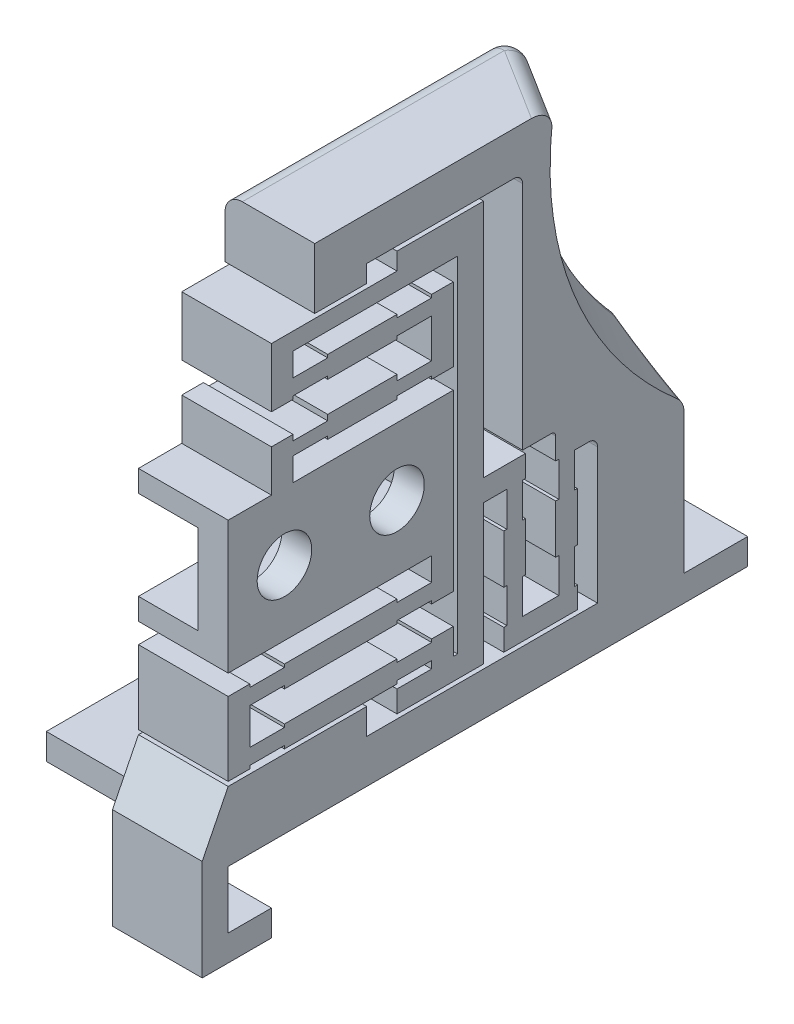
SolidWorks part; units mm, degrees
other "Markup1"
sketch "Sketch8" plane through (10.5, 0, 3) normal (0.7095, 0.0467, 0.7031) x (0.7044, -0.0184, -0.7096)
ref_plane "Front Plane" through (0, 0, 0) normal (0, 0, 1) x (1, 0, 0)
ref_plane "Top Plane" through (0, 0, 0) normal (0, 1, 0) x (1, 0, 0)
ref_plane "Right Plane" through (0, 0, 0) normal (1, 0, 0) x (0, 0, -1)
sketch "Sketch1" plane through (0, 0, 0) normal (1, 0, 0) x (0, 0, -1)
  line L0 (-1.25, -11.3333) -> (8, -11.3333)
  line L1 (8, -11.3333) -> (8, -21.4)
  line L2 (-5, -11.3333) -> (-5, -18.9833)
  line L3 (-5, -18.9833) -> (6.75, -18.9833)
  line L56 (6.75, -20.325) -> (4.75, -20.325)
  line L57 (-3.75, -21.225) -> (-3.75, -23.325)
  line L58 (-3.75, -23.325) -> (-1.75, -23.325)
  line L59 (8, -23.15) -> (8, -24.65)
  line L60 (6.75, -18.9833) -> (6.75, -20.325)
  line L61 (4.75, -20.325) -> (4.75, -20.15)
  line L62 (-5, -20.15) -> (-5, -24.4)
  line L63 (-1.75, -23.325) -> (-1.75, -23.15)
  line L64 (8.25, -4.75) -> (8.25, -24.65)
  line L65 (-1.25, -9.9917) -> (0.75, -9.9917)
  line L66 (6.75, -9.2417) -> (6.75, -6.9917)
  line L67 (6.75, -6.9917) -> (4.75, -6.9917)
  line L68 (-2.5, -7.1667) -> (-2.5, -3.75)
  line L69 (-1.25, -11.3333) -> (-1.25, -9.9917)
  line L70 (0.75, -9.9917) -> (0.75, -10.1667)
  line L71 (8, -10.1667) -> (8, -5.9167)
  line L72 (4.75, -6.9917) -> (4.75, -7.1667)
  line L73 (-1.25, -6.0917) -> (-1.25, -4.75)
  line L74 (-1.25, -4.75) -> (8.25, -4.75)
  line L75 (-2.5, -3.75) -> (4.75, -3.75)
  line L76 (0.75, -10.1667) -> (4.75, -10.1667)
  line L77 (4.75, -10.1667) -> (4.75, -9.9917)
  line L78 (4.75, -9.9917) -> (6.75, -9.9917)
  line L79 (6.75, -9.9917) -> (6.75, -10.1667)
  line L80 (6.75, -10.1667) -> (8, -10.1667)
  line L81 (6.75, -9.2417) -> (4.75, -9.2417)
  line L82 (4.75, -9.2417) -> (4.75, -8.9167)
  line L83 (4.75, -8.9167) -> (0.75, -8.9167)
  line L84 (0.75, -8.9167) -> (0.75, -9.2417)
  line L85 (0.75, -9.2417) -> (-1.25, -9.2417)
  line L86 (-1.25, -9.2417) -> (-1.25, -8.9167)
  line L87 (-1.25, -8.9167) -> (-2.5, -8.9167)
  line L88 (4.75, -7.1667) -> (0.75, -7.1667)
  line L89 (0.75, -7.1667) -> (0.75, -6.9917)
  line L90 (0.75, -6.9917) -> (-1.25, -6.9917)
  line L91 (-1.25, -6.9917) -> (-1.25, -7.1667)
  line L92 (-1.25, -7.1667) -> (-2.5, -7.1667)
  line L93 (-1.25, -6.0917) -> (0.75, -6.0917)
  line L94 (0.75, -6.0917) -> (0.75, -5.9167)
  line L95 (0.75, -5.9167) -> (4.75, -5.9167)
  line L96 (4.75, -5.9167) -> (4.75, -6.0917)
  line L97 (4.75, -6.0917) -> (6.75, -6.0917)
  line L98 (6.75, -6.0917) -> (6.75, -5.9167)
  line L99 (6.75, -5.9167) -> (8, -5.9167)
  line L100 (4.75, -20.15) -> (-1.75, -20.15)
  line L101 (-1.75, -20.15) -> (-1.75, -20.325)
  line L102 (-1.75, -20.325) -> (-3.75, -20.325)
  line L103 (-3.75, -20.325) -> (-3.75, -20.15)
  line L104 (-3.75, -20.15) -> (-5, -20.15)
  line L105 (8, -21.4) -> (6.75, -21.4)
  line L106 (6.75, -21.4) -> (6.75, -21.225)
  line L107 (6.75, -21.225) -> (4.75, -21.225)
  line L108 (4.75, -21.225) -> (4.75, -21.4)
  line L109 (4.75, -21.4) -> (-1.75, -21.4)
  line L110 (-1.75, -21.4) -> (-1.75, -21.225)
  line L111 (-1.75, -21.225) -> (-3.75, -21.225)
  line L112 (-1.75, -23.15) -> (4.75, -23.15)
  line L113 (4.75, -23.15) -> (4.75, -23.325)
  line L114 (4.75, -23.325) -> (6.75, -23.325)
  line L115 (6.75, -23.325) -> (6.75, -23.15)
  line L116 (6.75, -23.15) -> (8, -23.15)
  line L117 (-5, -24.4) -> (-3.75, -24.4)
  line L118 (-3.75, -24.4) -> (-3.75, -24.225)
  line L119 (-3.75, -24.225) -> (-1.75, -24.225)
  line L120 (-1.75, -24.225) -> (-1.75, -24.4)
  line L121 (-1.75, -24.4) -> (4.75, -24.4)
  line L122 (4.75, -24.4) -> (4.75, -24.225)
  line L123 (4.75, -24.225) -> (6.75, -24.225)
  line L124 (6.75, -24.225) -> (6.75, -24.65)
  line L125 (8.25, -24.65) -> (8, -24.65)
  line L126 (6.75, -24.65) -> (4.75, -24.65)
  line L127 (4.75, -24.65) -> (4.75, -25.9)
  line L128 (4.75, -25.9) -> (9.75, -25.9)
  line L130 (14.0917, -24.65) -> (11.9917, -24.65)
  line L131 (11.9917, -24.65) -> (11.9917, -22.65)
  line L132 (11.9917, -22.65) -> (12.1667, -22.65)
  line L133 (12.1667, -22.65) -> (12.1667, -19.8333)
  line L134 (12.1667, -19.8333) -> (11.9917, -19.8333)
  line L135 (11.9917, -19.8333) -> (11.9917, -17.8333)
  line L136 (11.9917, -17.8333) -> (12.1667, -17.8333)
  line L137 (14.0917, -17.8333) -> (14.0917, -19.8333)
  line L138 (14.0917, -19.8333) -> (13.9167, -19.8333)
  line L139 (13.9167, -19.8333) -> (13.9167, -22.65)
  line L140 (13.9167, -22.65) -> (14.0917, -22.65)
  line L141 (14.0917, -22.65) -> (14.0917, -24.65)
  line L145 (11.0917, -24.65) -> (10.9167, -24.65)
  line L146 (11.0917, -24.65) -> (11.0917, -22.65)
  line L147 (11.0917, -22.65) -> (10.9167, -22.65)
  line L148 (10.9167, -22.65) -> (10.9167, -19.8333)
  line L149 (10.9167, -19.8333) -> (11.0917, -19.8333)
  line L150 (11.0917, -17.8333) -> (9.75, -17.8333)
  line L151 (11.0917, -19.8333) -> (11.0917, -17.8333)
  line L153 (9.75, -16.5833) -> (12.1667, -16.5833)
  line L155 (15.8333, -17.8333) -> (14.9917, -17.8333)
  line L156 (14.9917, -17.8333) -> (14.9917, -19.8333)
  line L157 (14.9917, -19.8333) -> (15.1667, -19.8333)
  line L158 (15.1667, -19.8333) -> (15.1667, -22.65)
  line L159 (15.1667, -22.65) -> (14.9917, -22.65)
  line L160 (14.9917, -22.65) -> (14.9917, -24.65)
  line L168 (16.3333, -26.15) -> (16.3333, -18.3333)
  line L179 (16.3333, -26.15) -> (3, -26.15)
  line L180 (3, -26.15) -> (3, -24.65)
  line L181 (3, -24.65) -> (-5, -24.65)
  line L184 (-5, -28.65) -> (21.3333, -28.65)
  line L187 (21.3333, 0) -> (0, 0)
  line L189 (9.75, -25.9) -> (9.75, -17.8333)
  line L190 (3, -3.5) -> (0, -3.5)
  line L191 (0, -3.5) -> (0, 0)
  line L192 (15.1667, -24.65) -> (14.9917, -24.65)
  line L193 (13.6667, -16.3333) -> (12, -16.3333)
  line L194 (12, -16.3333) -> (12, -3)
  line L198 (10.9167, -24.65) -> (10.9167, -25.9)
  line L199 (15.1667, -24.65) -> (15.1667, -25.9)
  line L200 (15.1667, -25.9) -> (10.9167, -25.9)
  line L201 (9.75, -16.5833) -> (9.75, -2.75)
  line L203 (13.9167, -17.8333) -> (13.9167, -16.5833)
  line L204 (12.1667, -17.8333) -> (12.1667, -16.5833)
  line L205 (13.9167, -17.8333) -> (14.0917, -17.8333)
  line L208 (-5, -28.65) -> (-5, -31.98)
  line L209 (-5, -31.98) -> (-2.5, -31.98)
  line L210 (-2.5, -31.98) -> (-2.5, -33.48)
  line L211 (-2.5, -33.48) -> (-6.5, -33.48)
  line L212 (-6.5, -33.48) -> (-6.5, -27.65)
  line L213 (-6.5, -27.65) -> (-5, -24.65)
  line L214 (-2.5, -11.3333) -> (-5, -11.3333)
  line L215 (-2.5, -11.3333) -> (-2.5, -8.9167)
  line L216 (21.3333, 0) -> (21.3333, -28.65)
  line L217 (3, -3.5) -> (3, -2.5)
  line L218 (3, -2.5) -> (11.5, -2.5)
  line L219 (4.75, -3.75) -> (4.75, -2.75)
  line L220 (4.75, -2.75) -> (9.75, -2.75)
  arc A4 (15.8333, -17.8333) -> (16.3333, -18.3333) centre (15.8333, -18.3333) cw
  arc A5 (13.9167, -16.5833) -> (13.6667, -16.3333) centre (13.6667, -16.5833) ccw
  arc A6 (11.5, -2.5) -> (12, -3) centre (11.5, -3) cw
  point P120 (12, -3.5)
  point P140 (16.3333, -17.8333)
  point P144 (13.9167, -16.3333)
  point P159 (-1.875, -7.1667)
  point P199 (14.9917, -23.65)
  dimension "D61" = 0.5
  dimension "D62" = 0.25
  dimension "D66" = 0.5
  dimension "D3" = 4.25
  dimension "D4" = 0.175
  dimension "D5" = 1.25
  dimension "D6" = 0.9
  dimension "D7" = 1.75
  dimension "D8" = 0.175
  dimension "D9" = 0.9
  dimension "D10" = 1.1667
  dimension "D11" = 0.25
  dimension "D13" = 4.25
  dimension "D14" = 1.1667
  dimension "D15" = 0.175
  dimension "D16" = 1.25
  dimension "D17" = 0.75
  dimension "D18" = 1.75
  dimension "D19" = 0.175
  dimension "D21" = 0.9
  dimension "D22" = 1.1667
  dimension "D23" = 1
  dimension "D24" = 0.25
  dimension "D25" = 0.25
  dimension "D34" = 2.5
  dimension "D35" = 2
  dimension "D36" = 2
  dimension "D37" = 1.25
  dimension "D38" = 1.25
  dimension "D40" = 0.25
  dimension "D41" = 1.25
  dimension "D42" = 1.1667
  dimension "D43" = 0.175
  dimension "D44" = 0.9
  dimension "D45" = 1.75
  dimension "D46" = 0.175
  dimension "D47" = 0.9
  dimension "D48" = 1.25
  dimension "D12" = 7.65
  dimension "D20" = 1.5
  dimension "D26" = 1.25
  dimension "D27" = 1.1667
  dimension "D28" = 0.25
  dimension "D32" = 2
  dimension "D33" = 1.25
  dimension "D49" = 2.25
  dimension "D50" = 0.25
  dimension "D39" = 13
  dimension "D30" = 2
  dimension "D53" = 1.5
  dimension "D57" = 1.5
  dimension "D58" = 3.33
  dimension "D59" = 4
  dimension "D31" = 3.5
  dimension "D54" = 5
  dimension "D55" = 1.25
  dimension "D60" = 1
  dimension "D63" = 2
  dimension "D65" = 2.5
  dimension "D64" = 2.5
  dimension "D51" = 5
  dimension "D29" = 1.75
  dimension "D52" = 0.25
  dimension "D56" = 1
extrude "Boss-Extrude1" add sketch "Sketch1" along normal blind 5.18
sketch "Sketch2" plane through (0, 0, 5) normal (0, 0, 1) x (1, 0, 0)
  line L0 (5.18, -11.3333) -> (5.18, -18.9833) construction
  line L1 (5.18, -17.7333) -> (1.73, -17.7333)
  line L2 (5.18, -17.7333) -> (5.18, -12.5833)
  line L3 (5.18, -12.5833) -> (1.73, -12.5833)
  line L4 (1.73, -17.7333) -> (1.73, -12.5833)
  line L5 (5.18, -11.3333) -> (5.18, -18.9833) construction
  dimension "D1" = 3.45
  dimension "D2" = 1.25
  dimension "D3" = 1.25
extrude "Cut-Extrude4" cut sketch "Sketch2" against normal up to next
sketch "Sketch3" plane through (0, -28.65, 0) normal (0, -1, 0) x (1, 0, 0)
  line L1 (0, -25) -> (10.5, -25)
  line L2 (0, -25) -> (0, 5)
  line L3 (0, 5) -> (10.5, 5)
  line L4 (10.5, -25) -> (10.5, 5)
  line L5 (5.18, 5) -> (5.18, -21.3333) construction
  line L8 (0, 5) -> (0, -21.3333) construction
  circle A0 centre (7.92, -10.23) radius 1.575
  circle A1 centre (7.92, -22.23) radius 1.575
  dimension "D3" = 3.15
  dimension "D1" = 10.5
  dimension "D2" = 2.74
  dimension "D4" = 12
  dimension "D5" = 30
  dimension "D6" = 15.23
sketch "Sketch7" plane through (0, 0, 0) normal (-1, 0, 0) x (0, 0, 1)
  line L0 (2.5, -11.3333) -> (5, -11.3333) construction
  line L1 (5, -11.3333) -> (5, -18.9833) construction
  circle A0 centre (1.75, -15.2083) radius 1.575
  circle A1 centre (-4.75, -15.2083) radius 1.575
  dimension "D1" = 3.15
  dimension "D2" = 3.875
  dimension "D3" = 3.25
  dimension "D4" = 6.5
extrude "Cut-Extrude3" cut sketch "Sketch7" against normal up to next
extrude "Boss-Extrude2" add sketch "Sketch3" against normal blind 1.5
mirror "Mirror1" [suppressed] of bodies 111
delete or keep bodies "Body-Delete/Keep 1" [suppressed] type delete bodies bodies 111
ref_plane "Plane1" through (5.2923, 0, -3.3147) normal (-0.8475, 0, 0.5308) x (0, -1, 0)
sketch "Sketch10" plane through (5.2923, 0, -3.3147) normal (-0.8475, 0, 0.5308) x (0, -1, 0)
  line L1 (28.65, 4.2375) -> (28.65, -21.1873) construction
  line L2 (28.65, 9.8109) -> (28.65, -36.5965) construction
  circle A0 centre (3, -33.2691) radius 21.75
  dimension "D2" = 43.5
  dimension "D1" = 43.08
  dimension "D3" = 25.65
extrude "Cut-Extrude5" cut sketch "Sketch10" against normal blind 25
fillet "Fillet1" radius 1 5 edges at (2.7415, -17.0009, -21.3333) (2.59, 0, -15.4594) (5.18, -21.2244, -21.3333) (5.18, -7.9863, -17.5198) (5.18, 0, -8.5408)
mirror "Mirror2" about plane through (0, -18.3333, -15.8333) normal (-1, 0, 0) of bodies 113
delete or keep bodies "Body-Delete/Keep 2" type delete bodies bodies 113
equation "\"VerticalFlexureWidth\"= 1.3"
equation "\"VerticalFlexureGap\"= 1"
equation "\"VerticalDoubleFlexureWidth\"= 2 * \"VerticalFlexureWidth\" + \"VerticalFlexureGap\""
equation "\"HorizontalFlexureLength\"= 7"
equation "\"FlexureJointWidth\"= 1.25"
equation "\"HeadHeight\"= 7.5"
equation "\"VerticalFlexureLength\"= 18"
equation "\"MinGap\"= 0.25"
equation "\"BaseplateHeight+Tolerance\"= 3.33"
equation "\"HeadWidth\"= 13"
equation "\"D1@Boss-Extrude1\"=5.18"
equation "\"HorizontalFlexureWidth\"= 1"
equation "\"HorizontalFlexureGap\"= 1"
equation "\"HorizontalDoubleFlexureWidth\"= 2 * \"HorizontalFlexureWidth\" + \"HorizontalFlexureGap\""
equation "\"FlexureWidth\"= 0.9"
equation "\"FlexureWideWidth\"=1.25"
equation "\"FlexureGap\"=1.75"
equation "\"TwinFlexureWidth\"= \"FlexureGap\" + 2 * \"FlexureWideWidth\""
equation "\"D3@Sketch1\"=\"TwinFlexureWidth\""
equation "\"FlexureNeckWidth\"= ( \"FlexureWideWidth\" - \"FlexureWidth\" ) / 2"
equation "\"D4@Sketch1\"=\"FlexureNeckWidth\""
equation "\"D5@Sketch1\"=\"FlexureWideWidth\""
equation "\"D6@Sketch1\"=\"FlexureWidth\""
equation "\"D7@Sketch1\"=\"FlexureGap\""
equation "\"D8@Sketch1\"=\"FlexureNeckWidth\""
equation "\"D9@Sketch1\"=\"FlexureWidth\""
equation "\"D10@Sketch1\"=\"FlexureGapEdge\""
equation "\"D11@Sketch1\"=\"MinGap\""
equation "\"D13@Sketch1\"=\"TwinFlexureWidth\""
equation "\"D14@Sketch1\"=\"FlexureGapEdge\""
equation "\"D15@Sketch1\"=\"FlexureNeckWidth\""
equation "\"D16@Sketch1\"=\"FlexureWideWidth\""
equation "\"D19@Sketch1\"=\"FlexureNeckWidth\""
equation "\"D21@Sketch1\"=\"FlexureWidth\""
equation "\"D18@Sketch1\"=\"FlexureGap\""
equation "\"D22@Sketch1\"=\"FlexureGapEdge\""
equation "\"FlexureLength\"= 2"
equation "\"MainSupport\"=1.5"
equation "\"D24@Sketch1\"=\"MinGap\""
equation "\"D25@Sketch1\"=\"MinGap\""
equation "\"D35@Sketch1\"=\"FlexureLength\""
equation "\"D36@Sketch1\"=\"FlexureLength\""
equation "\"D37@Sketch1\"=\"FlexureJointWidth\""
equation "\"D38@Sketch1\"=\"FlexureJointWidth\""
equation "\"D40@Sketch1\"=\"MinGap\""
equation "\"D41@Sketch1\"=\"FlexureWideWidth\""
equation "\"D42@Sketch1\"=\"FlexureGapEdge\""
equation "\"D43@Sketch1\"=\"FlexureNeckWidth\""
equation "\"D44@Sketch1\"=\"FlexureWidth\""
equation "\"D46@Sketch1\"=\"FlexureNeckWidth\""
equation "\"D47@Sketch1\"=\"FlexureWidth\""
equation "\"D48@Sketch1\"=\"FlexureWideWidth\""
equation "\"D20@Sketch1\"=\"MainSupport\""
equation "\"D26@Sketch1\"=\"FlexureJointWidth\""
equation "\"D27@Sketch1\"=\"FlexureGapEdge\""
equation "\"D28@Sketch1\"=\"MinGap\""
equation "\"D32@Sketch1\"=\"FlexureLength\""
equation "\"D33@Sketch1\"=\"FlexureJointWidth\""
equation "\"D30@Sketch1\"=\"FlexureLength\""
equation "\"D53@Sketch1\"=\"MainSupport\""
equation "\"D57@Sketch1\"=\"MainSupport\""
equation "\"D58@Sketch1\"=\"BaseplateHeight+Tolerance\""
equation "\"D39@Sketch1\"=\"HeadWidth\""
equation "\"FlexureGapEdge\"= \"FlexureGap\" * ( 2 / 3 )"
equation "\"D55@Sketch1\"=\"FlexureJointWidth\""
equation "\"D63@Sketch1\"=\"FlexureLength\""
equation "\"FlexurePlateConnectionHeigh\"= 5.15 + 2.5"
equation "\"D12@Sketch1\"=\"FlexurePlateConnectionHeigh\""
equation "\"D45@Sketch1\"=\"FlexureGap\""
equation "\"D52@Sketch1\"=\"MinGap\""
